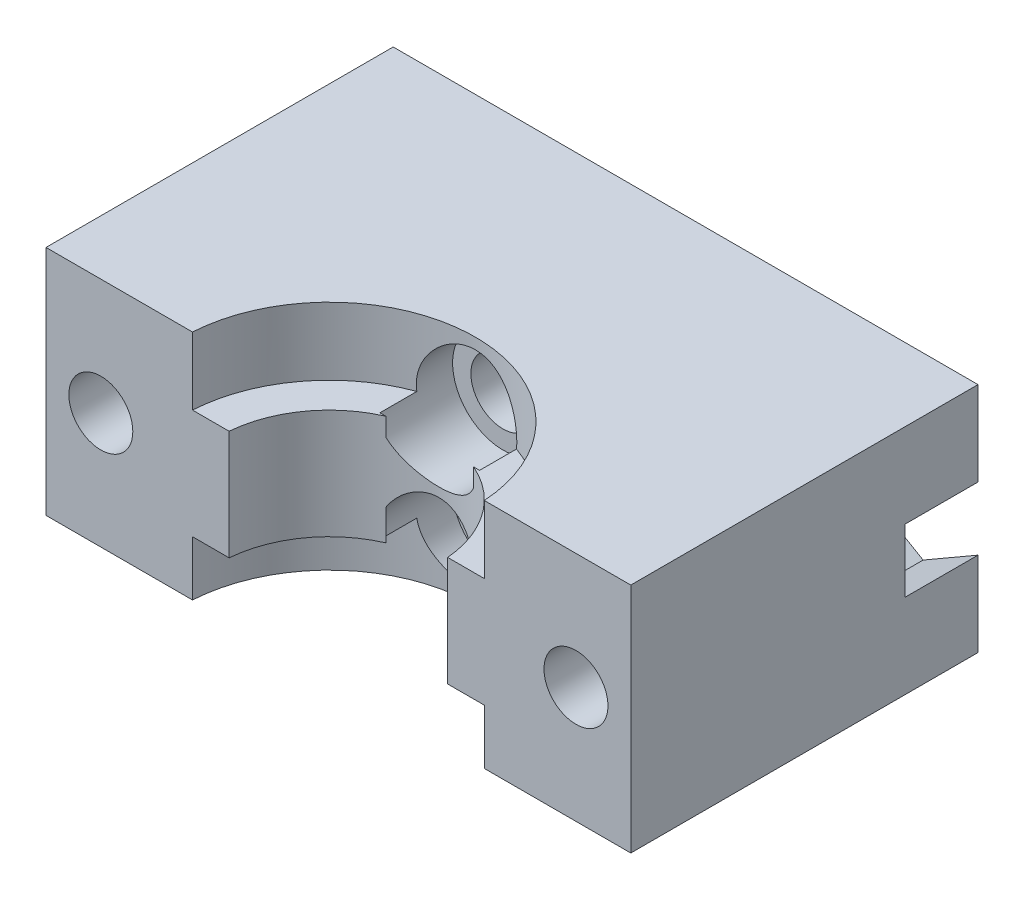
SolidWorks part; units mm, degrees
ref_plane "Front Plane" through (0, 0, 0) normal (0, 0, 1) x (1, 0, 0)
ref_plane "Top Plane" through (0, 0, 0) normal (0, 1, 0) x (1, 0, 0)
ref_plane "Right Plane" through (0, 0, 0) normal (1, 0, 0) x (0, 0, -1)
sketch "Sketch2" plane through (0, 0, 0) normal (0, 0, 1) x (1, 0, 0)
  line L0 (0, -3) -> (0, 3) construction
  line L1 (-16, 6.35) -> (16, 6.35)
  line L2 (-16, 6.35) -> (-16, -6.35)
  line L3 (-16, -6.35) -> (16, -6.35)
  line L4 (16, 6.35) -> (16, -6.35)
  line L5 (-16, 6.35) -> (16, -6.35) construction
  line L6 (-16, -6.35) -> (16, 6.35) construction
  circle A0 centre (0, 3) radius 1.75
  circle A1 centre (0, -3) radius 1.75
  point P0 (0, 0)
  dimension "D3" = 3.5
  dimension "D1" = 32
  dimension "D2" = 12.7
  dimension "D4" = 6
extrude "Boss-Extrude1" add sketch "Sketch2" along normal blind 19
sketch "Sketch3" plane through (0, 0, 19) normal (0, 0, 1) x (1, 0, 0)
  line L0 (16, 6.35) -> (-16, 6.35) construction
  line L5 (-16, -6.35) -> (16, -6.35) construction
  line L6 (-16, 6.35) -> (-10, 6.35) construction
  line L7 (-13, 6.35) -> (-13, -6.35) construction
  line L8 (10, 6.35) -> (16, 6.35) construction
  line L9 (13, 6.35) -> (13, -6.35) construction
  circle A0 centre (-13, 0) radius 1.75
  circle A1 centre (13, 0) radius 1.75
  point P1 (-8.2541, 6.35)
  point P23 (11.4408, 0)
  point P24 (11.8377, 6.35)
  point P25 (8.2036, 6.35)
  dimension "D2" = 3.5
  dimension "D1" = 6
  dimension "D3" = 6
extrude "Cut-Extrude1" cut sketch "Sketch3" against normal through all
sketch "Sketch4" plane through (0, 0, 0) normal (0, 0, -1) x (-1, 0, 0)
  line L1 (-10, -1.7321) -> (-10, 1.7321)
  line L2 (-10, 1.7321) -> (-13, 3.4641)
  line L3 (-13, 3.4641) -> (-16, 1.7321)
  line L4 (-16, 1.7321) -> (-16, -1.7321)
  line L5 (-16, -1.7321) -> (-13, -3.4641)
  line L6 (-13, -3.4641) -> (-10, -1.7321)
  line L7 (13, -3.4641) -> (16, -1.7321)
  line L8 (16, -1.7321) -> (16, 1.7321)
  line L9 (16, 1.7321) -> (13, 3.4641)
  line L10 (13, 3.4641) -> (10, 1.7321)
  line L11 (10, 1.7321) -> (10, -1.7321)
  line L12 (10, -1.7321) -> (13, -3.4641)
  line L13 (-16, -6.35) -> (-16, 6.35) construction
  circle A0 centre (-13, 0) radius 3 construction
  circle A1 centre (13, 0) radius 3 construction
  point P10 (0, 0)
  point P19 (-14.4, 1.6743)
  point P21 (0, 0)
  dimension "D1" = 6
extrude "Cut-Extrude2" cut sketch "Sketch4" against normal blind 4
sketch "Sketch5" plane through (0, 6.35, 0) normal (0, 1, 0) x (1, 0, 0)
  line L0 (16, 0) -> (-16, 0) construction
  circle A0 centre (0, -19.5) radius 8
  point P2 (0, -16.4284)
  point P5 (0, 0)
  dimension "D1" = 16
  dimension "D2" = 19.5
extrude "Cut-Extrude3" cut sketch "Sketch5" against normal blind 3.7
sketch "Sketch9" plane through (0, 2.65, 0) normal (0, 1, 0) x (1, 0, 0)
  circle A0 centre (0, -19.5) radius 6
  dimension "D1" = 12
extrude "Cut-Extrude5" cut sketch "Sketch9" against normal blind 6
sketch "Sketch10" plane through (0, -3.35, 0) normal (0, 1, 0) x (1, 0, 0)
  circle A0 centre (0, -19.5) radius 8
  dimension "D1" = 16
extrude "Cut-Extrude6" cut sketch "Sketch10" against normal through all
ref_plane "Plane1" through (0, 0, 14) normal (0, 0, 1) x (1, 0, 0)
sketch "Sketch6" plane through (0, 0, 14) normal (0, 0, 1) x (1, 0, 0)
  circle A0 centre (0, 3) radius 2.75
  circle A1 centre (0, -3) radius 2.75
  dimension "D1" = 5.5
  dimension "D2" = 5.5
extrude "Cut-Extrude4" cut sketch "Sketch6" against normal blind 4
